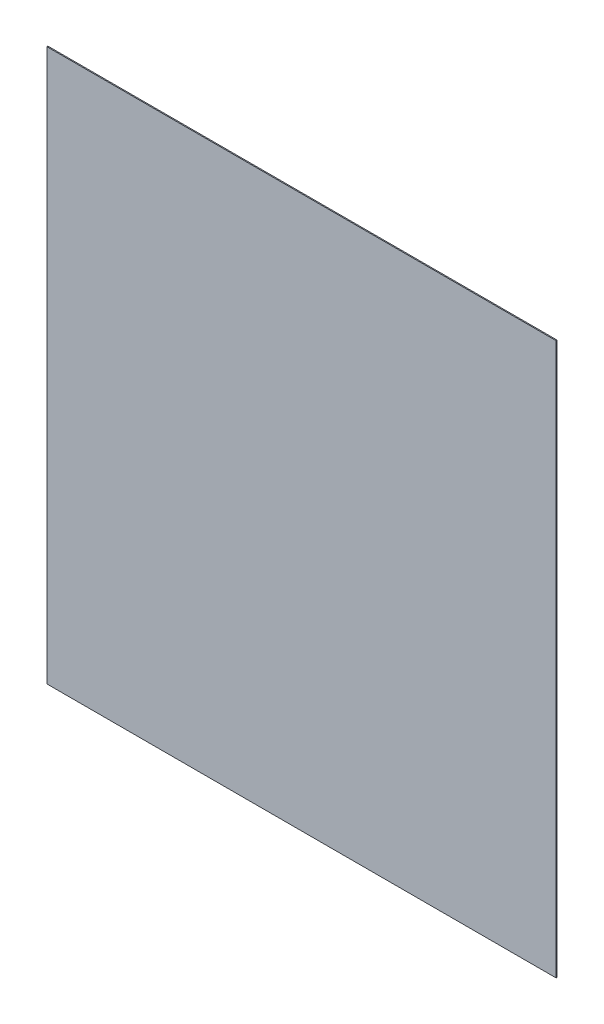
SolidWorks part; units mm, degrees
material "AISI 304"
ref_plane "Front Plane" through (0, 0, 0) normal (0, 0, 1) x (1, 0, 0)
ref_plane "Top Plane" through (0, 0, 0) normal (0, 1, 0) x (1, 0, 0)
ref_plane "Right Plane" through (0, 0, 0) normal (1, 0, 0) x (0, 0, -1)
sketch "Sketch1" plane through (0, 0, 0) normal (0, 0, 1) x (1, 0, 0)
  line L1 (300, -325) -> (-300, -325)
  line L2 (300, -325) -> (300, 325)
  line L3 (300, 325) -> (-300, 325)
  line L4 (-300, -325) -> (-300, 325)
  line L5 (300, -325) -> (-300, 325) construction
  line L6 (300, 325) -> (-300, -325) construction
  point P0 (0, 0)
  dimension "D1" = 650
  dimension "D2" = 600
base flange "Base-Flange1" sketch "Sketch1" thickness 1.2 reverse thickness direction no parameters "D1"=0.7366
sketch "Bend-Lines1" [suppressed] plane through (0, 0, 0) normal (0, 1, 0) x (1, 0, 0)
sketch "Bounding-Box1" [suppressed] plane through (0, 0, 0) normal (0, 1, 0) x (1, 0, 0)
sheet metal parameters "Sheet-Metal1" thickness 1.2 parameters "D1"=0.7366
flat pattern "Flat-Pattern1" [suppressed]
sketch "Bend-Lines2" plane through (0, 0, 0) normal (0, 1, 0) x (1, 0, 0)
sketch3d "Bounding-Box2" [suppressed]
  line L0 (-300, 325, 0) -> (-300, -325, 0) construction
  line L1 (300, 325, 0) -> (300, -325, 0) construction
  line L2 (-300, 325, 0) -> (300, 325, 0) construction
  line L3 (-300, -325, 0) -> (300, -325, 0) construction
